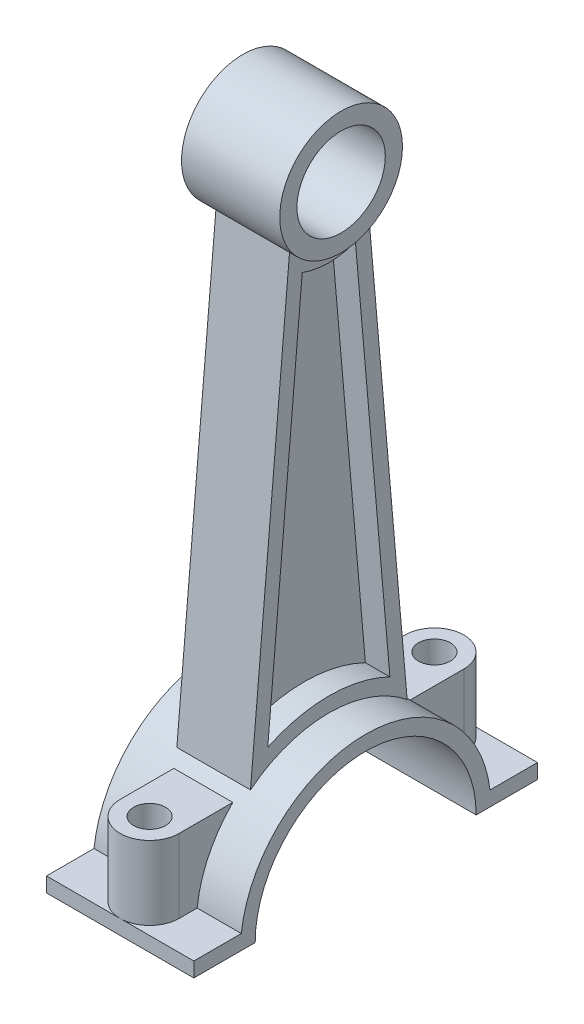
SolidWorks part; units mm, degrees
ref_plane "Front Plane" through (0, 0, 0) normal (0, 0, 1) x (1, 0, 0)
ref_plane "Top Plane" through (0, 0, 0) normal (0, 1, 0) x (1, 0, 0)
ref_plane "Right Plane" through (0, 0, 0) normal (1, 0, 0) x (0, 0, -1)
sketch "Sketch1" plane through (0, 0, 0) normal (1, 0, 0) x (0, 0, -1)
  line L0 (22.5, -120.4) -> (35, -120.4)
  line L1 (-22.5, -120.4) -> (-35, -120.4)
  line L2 (25.3229, -117.4) -> (35, -117.4)
  line L3 (-25.3229, -117.4) -> (-35, -117.4)
  line L4 (-35, -120.4) -> (-35, -117.4)
  line L5 (35, -120.4) -> (35, -117.4)
  line L6 (-8, -9.6047) -> (-15.9529, -100.5064)
  line L7 (0, 0) -> (0, -120.4) construction
  line L8 (8, -9.6047) -> (15.9529, -100.5064)
  circle A0 centre (0, 0) radius 12.5
  circle A1 centre (0, 0) radius 9
  arc A2 (22.5, -120.4) -> (-22.5, -120.4) centre (0, -120.4) ccw
  arc A3 (25.3229, -117.4) -> (-25.3229, -117.4) centre (0, -120.4) ccw
  dimension "D1" = 25
  dimension "D2" = 18
  dimension "D3" = 45
  dimension "D4" = 120.4
  dimension "D5" = 35
  dimension "D7" = 8
  dimension "D8" = 5
  dimension "D6" = 3
extrude "Boss-Extrude1" add sketch "Sketch1" along normal mid plane 20 contours A1 A0 region at (0, -12.1464, 0)
extrude "Boss-Extrude2" add sketch "Sketch1<3>" along normal mid plane 30 separate body contours A3 L3 L4 L1 A2 L0 L5 L2
sketch "Sketch1<3>" plane through (0, 0, 0) normal (1, 0, 0) x (0, 0, -1) same geometry as "Sketch1"
extrude "Boss-Extrude3" add sketch "Sketch1<7>" along normal mid plane 15 contours L7 A0 L6 A3 | A0 L7 A3 L8 region at (0, -58.5545, 6.2653) region at (0, -58.5545, -6.2653)
sketch "Sketch1<7>" plane through (0, 0, 0) normal (1, 0, 0) x (0, 0, -1) same geometry as "Sketch1"
sketch "Sketch2" plane through (0, -117.4, 0) normal (0, 1, 0) x (1, 0, 0)
  line L0 (0, 0) -> (0, 35) construction
  line L1 (15, 35) -> (-15, 35) construction
  line L4 (-6, 29) -> (-6, 17)
  line L5 (-6, 17) -> (6, 17)
  line L6 (6, 29) -> (6, 17)
  arc A0 (6, 29) -> (-6, 29) centre (0, 29) ccw
  dimension "D1" = 6
  dimension "D2" = 12
extrude "Boss-Extrude4" add sketch "Sketch2" along normal blind 15
sketch "Sketch3" plane through (0, -102.4, 0) normal (0, 1, 0) x (1, 0, 0)
  circle A0 centre (0, 29) radius 3.25
  dimension "D1" = 6.5
extrude "Cut-Extrude1" cut sketch "Sketch3" against normal through all
mirror "Mirror1" about plane through (0, 0, 0) normal (0, 0, 1) of "Cut-Extrude1", "Boss-Extrude4"
sketch "Sketch4" plane through (15, 0, 0) normal (1, 0, 0) x (0, 0, -1)
  circle A0 centre (0, -120.4) radius 22.5
extrude "Cut-Extrude2" cut sketch "Sketch4" against normal blind 151
sketch "Sketch5" plane through (7.5, 0, 0) normal (1, 0, 0) x (0, 0, -1)
  line L0 (8, -9.6047) -> (15.9529, -100.5064) construction
  line L1 (-8, -9.6047) -> (-15.9529, -100.5064) construction
  line L2 (8, -9.6047) -> (15.9529, -100.5064)
  line L3 (-8, -9.6047) -> (-15.9529, -100.5064)
  line L4 (5.4187, -14.522) -> (12.4385, -94.7576)
  line L5 (-5.4187, -14.522) -> (-12.4385, -94.7576)
  arc A0 (15.9529, -100.5064) -> (-15.9529, -100.5064) centre (0, -120.4) ccw construction
  circle A1 centre (0, 0) radius 12.5 construction
  arc A2 (15.9529, -100.5064) -> (-15.9529, -100.5064) centre (0, -120.4) ccw
  arc A3 (-8, -9.6047) -> (8, -9.6047) centre (0, 0) ccw
  arc A4 (-5.4187, -14.522) -> (5.4187, -14.522) centre (0, 0) ccw
  arc A5 (12.4385, -94.7576) -> (-12.4385, -94.7576) centre (0, -120.4) ccw
  dimension "D1" = 3
extrude "Cut-Extrude3" cut sketch "Sketch5" against normal blind 5 contours A5 L4 A4 L5 region at (7.5, -58.957, 0)
mirror "Mirror2" about plane through (0, 0, 0) normal (1, 0, 0) of "Cut-Extrude3"
